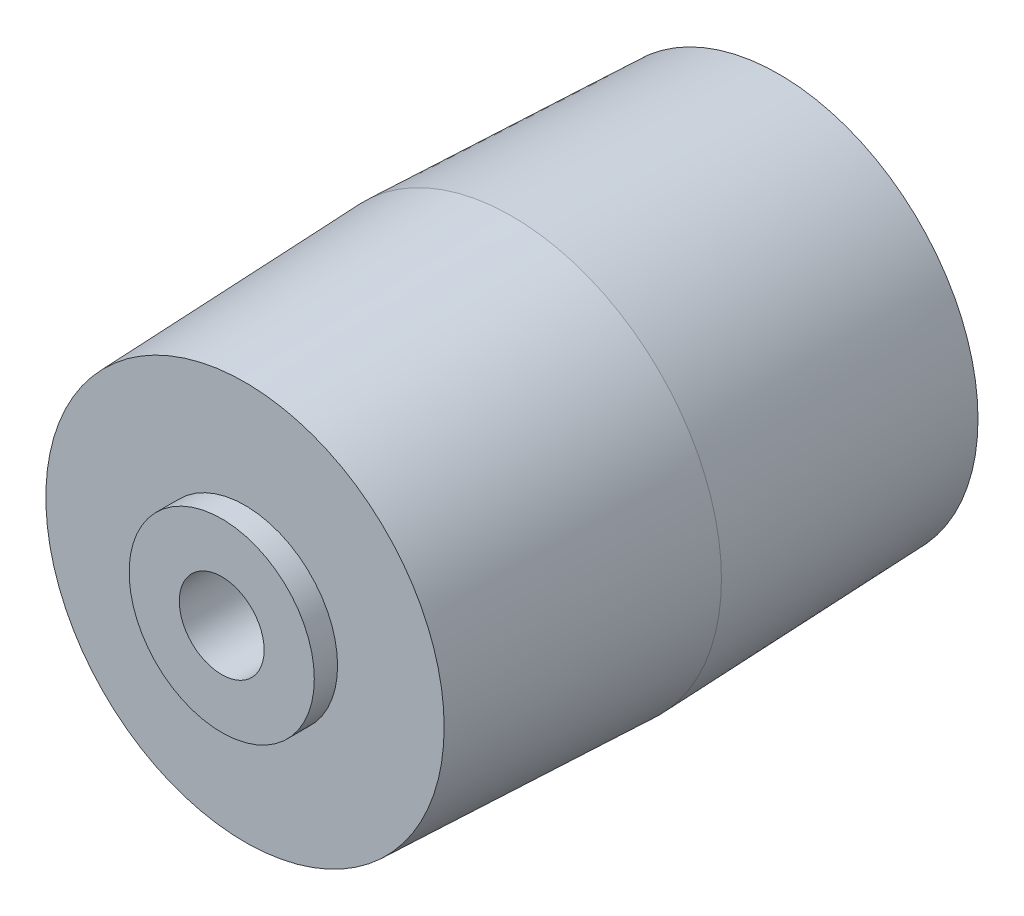
SolidWorks part; units mm, degrees
ref_plane "Front Plane" through (0, 0, 0) normal (0, 0, 1) x (1, 0, 0)
ref_plane "Top Plane" through (0, 0, 0) normal (0, 1, 0) x (1, 0, 0)
ref_plane "Right Plane" through (0, 0, 0) normal (1, 0, 0) x (0, 0, -1)
sketch "Sketch1" plane through (0, 0, 0) normal (1, 0, 0) x (0, 0, -1)
  line L0 (-7.1247, 0) -> (-7.1247, 2.2733)
  line L1 (-7.1247, 2.2733) -> (-6.5532, 2.2733)
  line L2 (-6.5532, 2.2733) -> (-6.5532, 4.8895)
  line L3 (-6.5532, 4.8895) -> (0, 5.1435)
  line L4 (0, 0) -> (0, 5.1435) construction
  line L5 (7.1247, 0) -> (-7.1247, 0) construction
  line L6 (6.5532, 4.8895) -> (0, 5.1435)
  line L7 (6.5532, 2.2733) -> (6.5532, 4.8895)
  line L8 (7.1247, 2.2733) -> (6.5532, 2.2733)
  line L9 (7.1247, 0) -> (7.1247, 2.2733)
  line L10 (-7.1247, 0) -> (7.1247, 0)
  dimension "D1" = 14.2494
  dimension "D2" = 13.1064
  dimension "D3" = 10.287
  dimension "D4" = 9.779
  dimension "D5" = 4.5466
revolve "Revolve1" add sketch "Sketch1" angle 360 about L10
sketch "Sketch2" plane through (0, 0, 7.1247) normal (0, 0, 1) x (1, 0, 0)
  circle A0 centre (0, 0) radius 1.0414
  dimension "D1" = 2.0828
extrude "Cut-Extrude1" cut sketch "Sketch2" against normal through all
